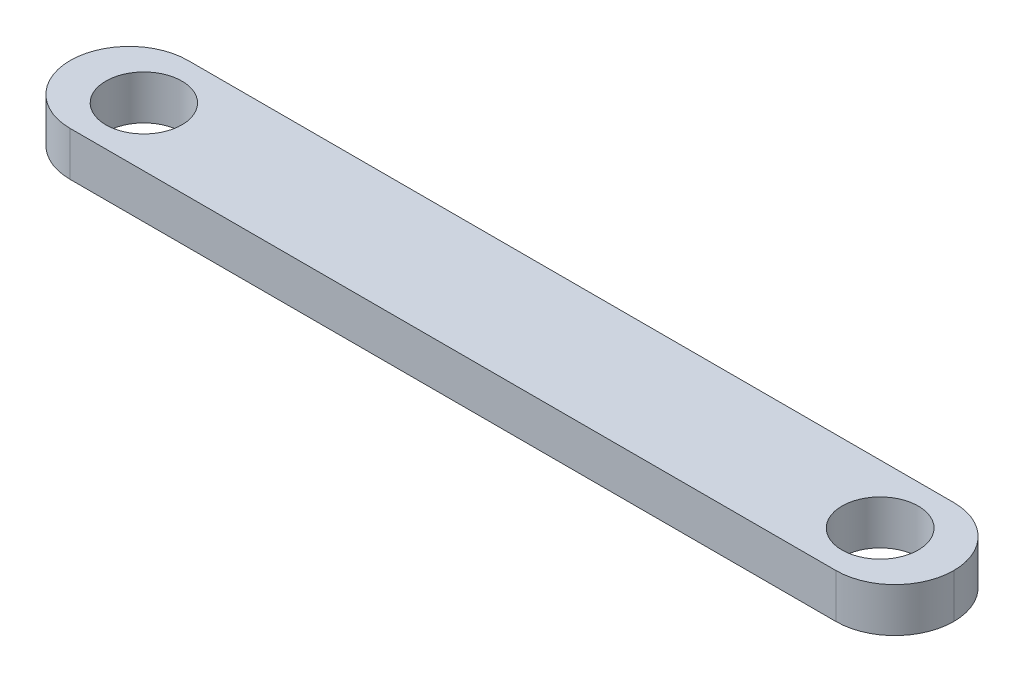
SolidWorks part; units mm, degrees
ref_plane "Front Plane" through (0, 0, 0) normal (0, 0, 1) x (1, 0, 0)
ref_plane "Top Plane" through (0, 0, 0) normal (0, 1, 0) x (1, 0, 0)
ref_plane "Right Plane" through (0, 0, 0) normal (1, 0, 0) x (0, 0, -1)
sketch "Sketch1" plane through (0, 0, 0) normal (0, 1, 0) x (1, 0, 0)
  line L0 (-30, 0) -> (30, 0) construction
  line L1 (-30, -4) -> (30, -4)
  line L2 (-30, -4) -> (-30, 4)
  line L3 (-30, 4) -> (30, 4)
  line L4 (30, -4) -> (30, 4)
  line L7 (0, 4) -> (0, -4) construction
  line L8 (-25, 4) -> (-25, -4) construction
  line L9 (25, 4) -> (25, -4) construction
  circle A0 centre (-25, 0) radius 2.58
  circle A1 centre (25, 0) radius 2.59
  point P0 (0, 0)
  point P19 (0, 0)
  dimension "D5" = 5
  dimension "D4" = 25
  dimension "D1" = 60
  dimension "D2" = 8
  dimension "D3" = 50
extrude "Boss-Extrude1" add sketch "Sketch1" along normal blind 3
fillet "Redondeo2" radius 4 4 edges at (30, 1.5, -4) (30, 1.5, 4) (-30, 1.5, -4) (-30, 1.5, 4)
